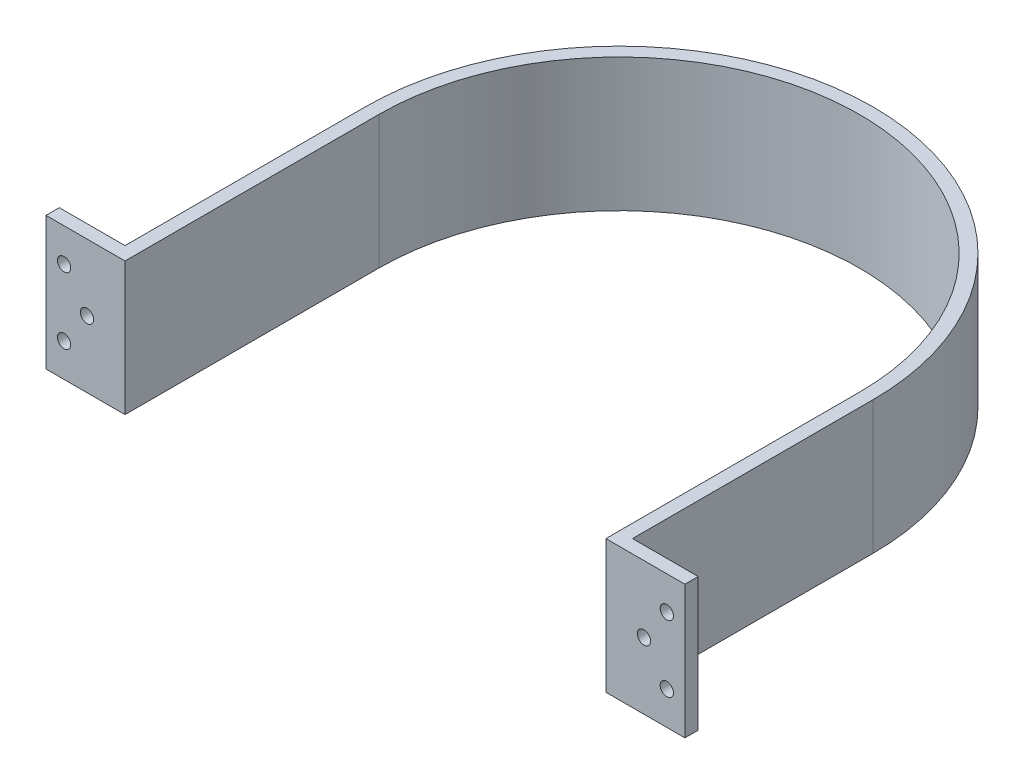
SolidWorks part; units mm, degrees
other "Markup1"
sketch "Sketch14" plane through (-178.835, 31.75, 121.05) normal (-0.0444, 0.3923, 0.9187) x (0.9976, 0.0664, 0.0198)
ref_plane "Front Plane" through (0, 0, 0) normal (0, 0, 1) x (1, 0, 0)
ref_plane "Top Plane" through (0, 0, 0) normal (0, 1, 0) x (1, 0, 0)
ref_plane "Right Plane" through (0, 0, 0) normal (1, 0, 0) x (0, 0, -1)
sketch "Sketch1" plane through (0, 0, 0) normal (0, 1, 0) x (1, 0, 0)
  line L0 (0, 0) -> (-121.05, 0) construction
  line L1 (0, 0) -> (0, -121.05) construction
  line L2 (0, -121.05) -> (-152.4, -121.05)
  line L3 (-114.7, 0) -> (-114.7, -121.05)
  line L4 (-121.05, 0) -> (-121.05, -121.05)
  line L5 (0, -114.7) -> (-152.4, -114.7)
  line L6 (-152.4, -114.7) -> (-152.4, -121.05)
  line L7 (-120.3819, -12.7) -> (-121.05, -12.7)
  line L8 (152.4, -114.7) -> (152.4, -121.05)
  line L9 (0, -114.7) -> (152.4, -114.7)
  line L10 (-113.9947, -12.7) -> (-114.7, -12.7)
  line L11 (121.05, 0) -> (121.05, -121.05)
  line L12 (114.7, 0) -> (114.7, -121.05)
  line L13 (0, -121.05) -> (152.4, -121.05)
  circle A0 centre (0, 0) radius 102
  circle A1 centre (0, 0) radius 114.7
  arc A3 (-114.7, -38.6912) -> (-121.05, 0) centre (0, 0) ccw
  arc A4 (-114.7, -38.6912) -> (119.5416, -19.05) centre (0, 0) ccw
  arc A5 (120.3819, -12.7) -> (120.3819, 12.7) centre (0, 0) ccw
  circle A6 centre (0, 0) radius 121.05 construction
  point P8 (-152.4, -117.875)
  point P29 (0, 0)
  dimension "D1" = 204
  dimension "D2" = 12.7
  dimension "D4" = 152.4
  dimension "D3" = 6.35
  dimension "D5" = 6.35
extrude "Boss-Extrude1" add sketch "Sketch1" along normal mid plane 63.5 contours L5 L6 L2 L4 | L3 L5 L4 L2 | L12 A3 L4 L5 L3 A1 | A3 L12 L9 L11 | L12 L13 L11 L9 | L11 L13 L8 L9 region at (-117.875, 0, 117.875) region at (117.875, 0, 117.875) region at (-136.725, 0, 117.875) region at (-117.875, 0, 111.3208) region at (118.0588, 0, 69.8503) region at (136.725, 0, 117.875)
sketch "Sketch15" plane through (0, 0, 121.05) normal (0, 0, 1) x (1, 0, 0)
  line L0 (-138.3125, 0) -> (-127.4, 0) construction
  line L5 (-127.4, 31.75) -> (-127.4, -31.75)
  line L6 (-127.4, 31.75) -> (-127.4, -31.75)
  line L7 (-138.3125, 0) -> (-138.3125, 31.75) construction
  line L8 (-149.225, 31.75) -> (-149.225, -31.75)
  line L9 (-149.225, 31.75) -> (-149.225, -31.75)
  line L10 (-114.7, 31.75) -> (-152.4, 31.75) construction
  line L11 (-138.3125, 15.875) -> (-149.225, 15.875) construction
  line L12 (0, 0) -> (0, 31.75) construction
  line L13 (114.7, 31.75) -> (-114.7, 31.75) construction
  circle A0 centre (-143.7688, 15.875) radius 3.175
  circle A1 centre (-143.7688, -15.875) radius 3.175
  circle A2 centre (-132.8563, 0) radius 3.175
  circle A3 centre (132.8563, 0) radius 3.175
  circle A4 centre (143.7688, -15.875) radius 3.175
  circle A5 centre (143.7688, 15.875) radius 3.175
  dimension "D1" = 12.7
  dimension "D2" = 3.175
extrude "Cut-Extrude1" cut sketch "Sketch15" against normal through all contours A0 | A2 | A1 | A3 | A5 | A4
